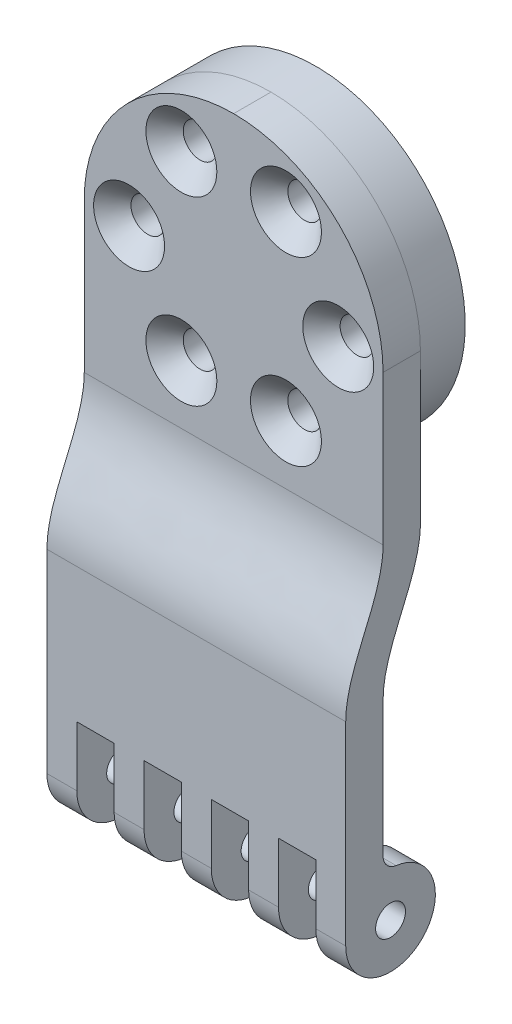
SolidWorks part; units mm, degrees
other "Markup1"
sketch "Sketch13" plane through (20, -53, 11) normal (0.0614, -0.6805, 0.7302) x (0.9699, -0.1321, -0.2046)
sketch "Sketch20" plane through (20.0001, -70, 16.0001) normal (0.0614, -0.6805, 0.7302) x (0.9699, -0.1321, -0.2046)
ref_plane "Front Plane" through (0, 0, 0) normal (0, 0, 1) x (1, 0, 0)
ref_plane "Top Plane" through (0, 0, 0) normal (0, 1, 0) x (1, 0, 0)
ref_plane "Right Plane" through (0, 0, 0) normal (1, 0, 0) x (0, 0, -1)
sketch "Sketch7" plane through (0, 0, 0) normal (0, 0, 1) x (1, 0, 0)
  line L1 (-20, 20) -> (20, 20)
  line L2 (-20, 20) -> (-20, -20)
  line L3 (-20, -20) -> (20, -20)
  line L4 (20, 20) -> (20, -20)
  line L5 (-20, 20) -> (20, -20) construction
  line L6 (-20, -20) -> (20, 20) construction
  point P0 (0, 0)
extrude "Boss-Extrude1" add sketch "Sketch7" along normal blind 11
ref_plane "Plane2" through (0, -21.4103, 5.7369) normal (0, -0.9659, 0.2588) x (1, 0, 0)
sketch "Sketch8" plane through (0, -20, 2.0782) normal (0, -1, 0) x (1, 0, 0)
  line L0 (20, 8.9218) -> (20, -2.0782) construction
  line L1 (-20, 8.9218) -> (20, 8.9218)
  line L2 (-20, 8.9218) -> (-20, 3.9218)
  line L3 (-20, 3.9218) -> (20, 3.9218)
  line L4 (20, 8.9218) -> (20, 3.9218)
  line L5 (0, 3.9218) -> (0, 8.9218) construction
  line L6 (-20, 6.4218) -> (20, 6.4218) construction
  line L7 (-20, -2.0782) -> (20, -2.0782) construction
  point P764 (0, 6.4218)
  dimension "D1" = 6
ref_plane "Plane4" through (0, -38, 0) normal (0, -1, 0) x (-1, 0, 0)
sketch "Sketch19" plane through (0, -38, 0) normal (0, -1, 0) x (-1, 0, 0)
  line L0 (20, -11) -> (20, 0) construction
  line L1 (20, -16) -> (-20, -16)
  line L2 (20, -16) -> (20, -11)
  line L3 (20, -11) -> (-20, -11)
  line L4 (-20, -16) -> (-20, -11)
  line L5 (20, -16) -> (-20, -11) construction
  line L6 (20, -11) -> (-20, -16) construction
  line L7 (-20, -11) -> (-20, 0) construction
  line L8 (20, -11) -> (-20, -11) construction
  point P4 (0, -13.5)
  dimension "D1" = 5
  dimension "D2" = 5
loft "Loft1" add profiles "Sketch19", "Sketch8" start constraint normal to profile start tangent length 1 end constraint normal to profile end tangent length 1 connector at (-20, -38, 16) connector at (-20, -20, 11)
sketch "Sketch16" plane through (0, 0, 0) normal (0, 0, -1) x (-1, 0, 0)
  line L1 (24.5131, 32.6211) -> (-24.5131, 32.6211)
  line L2 (24.5131, 32.6211) -> (24.5131, -32.6211)
  line L3 (24.5131, -32.6211) -> (-24.5131, -32.6211)
  line L4 (-24.5131, 32.6211) -> (-24.5131, -32.6211)
  line L5 (24.5131, 32.6211) -> (-24.5131, -32.6211) construction
  line L6 (24.5131, -32.6211) -> (-24.5131, 32.6211) construction
  circle A0 centre (0, 0) radius 20
extrude "Cut-Extrude3" cut sketch "Sketch16" against normal blind 6
ref_plane "Plane3" [suppressed] through (0, -56, 0) normal (0, -1, 0) x (-1, 0, 0)
sketch "Sketch17" plane through (0, -38, 0) normal (0, -1, 0) x (-1, 0, 0)
  line L1 (20, -16) -> (-20, -16)
  line L2 (20, -16) -> (20, -11)
  line L3 (20, -11) -> (-20, -11)
  line L4 (-20, -16) -> (-20, -11)
  line L5 (20, -16) -> (-20, -11) construction
  line L6 (20, -11) -> (-20, -16) construction
  line L10 (-20, -16) -> (20, -16) construction
  line L11 (-20, -6) -> (-20, -11) construction
  line L12 (20, -11) -> (20, -6) construction
  point P4 (0, -13.5)
  dimension "D1" = 5
extrude "Boss-Extrude5" add sketch "Sketch17" along normal blind 18
sketch "Sketch10" plane through (0, 0, 11) normal (0, 0, 1) x (1, 0, 0)
  circle A0 centre (-7.0001, 12.1244) radius 2.25
  circle A1 centre (6.9999, 12.1244) radius 2.25
  circle A2 centre (13.9999, 0.0001) radius 2.25
  circle A3 centre (6.9999, -12.1243) radius 2.25
  circle A4 centre (-7.0001, -12.1243) radius 2.25
  circle A5 centre (-14.0001, 0.0001) radius 2.25
  point P0 (0, 0)
  point P1 (0.0025, 0.0011)
  dimension "D4" = 4.5
extrude "Cut-Extrude1" cut sketch "Sketch10" against normal blind 25
sketch "Sketch11" plane through (0, -56, -3.473) normal (0, 1, 0) x (1, 0, 0)
  line L1 (-20, -14.473) -> (-16, -14.473)
  line L2 (-20, -14.473) -> (-20, -19.473)
  line L3 (-20, -19.473) -> (-16, -19.473)
  line L4 (-16, -14.473) -> (-16, -19.473)
  line L5 (-18, -19.473) -> (-18, -14.473) construction
  line L6 (-20, -16.973) -> (-16, -16.973) construction
  line L11 (-20, -14.473) -> (20, -14.473) construction
  line L12 (-20, -14.473) -> (-20, -9.473) construction
  line L13 (20, -19.473) -> (-20, -19.473) construction
  point P368 (-18, -16.973)
  dimension "D1" = 4
extrude "Boss-Extrude3" add sketch "Sketch11" against normal blind 8 contours L1 L4 L3 L2
ref_plane "Plane1" through (-16, 0, 0) normal (1, 0, 0) x (0, 0, -1)
sketch "Sketch14" plane through (-16, 0, 0) normal (1, 0, 0) x (0, 0, -1)
  line L0 (-16, -64) -> (-11, -64) construction
  line L7 (-16, -64) -> (-16, -38) construction
  circle A0 centre (-10, -64) radius 6
  dimension "D3" = 12
  dimension "D1" = 0
extrude "Boss-Extrude4" add sketch "Sketch14" against normal up to vertex (4 mm away) up to point (-20, -20, 11)
pattern_linear "LPattern1" count 5 spacing 9 along (1, 0, 0) of "Boss-Extrude4", "Boss-Extrude3"
sketch "Sketch15" plane through (-20, 0, 0) normal (-1, 0, 0) x (0, 0, 1)
  circle A0 centre (10, -64) radius 2
extrude "Cut-Extrude2" cut sketch "Sketch15" against normal through all
chamfer "Chamfer1" distance 2.5 angle 45 6 edges at (-4.7501, 12.1244, 11) (-11.7501, 0.0001, 11) (-4.7501, -12.1243, 11) (9.2499, 12.1244, 11) (16.2499, 0.0001, 11) (9.2499, -12.1243, 11)
fillet "Fillet2" radius 2 5 edges at (-18, -58.0839, 11) (-9, -58.0839, 11) (0, -58.0839, 11) (9, -58.0839, 11) (18, -58.0839, 11)
fillet "Fillet3" radius 20 2 edges at (20, 20, 8.5) (-20, 20, 8.5)
